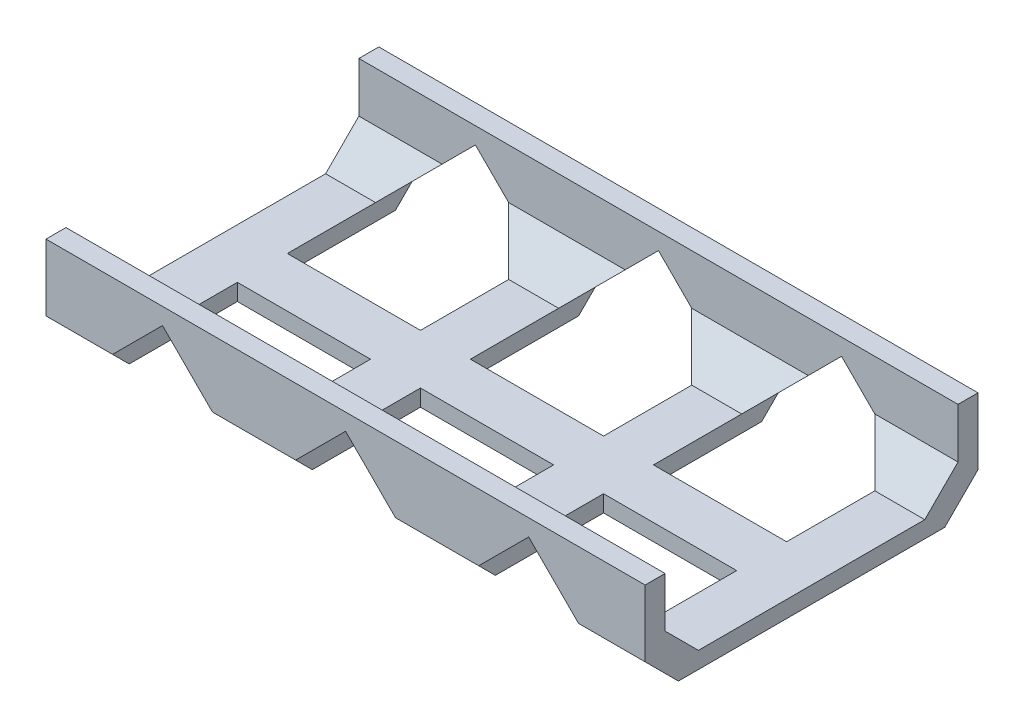
SolidWorks part; units mm, degrees
ref_plane "Front Plane" through (0, 0, 0) normal (0, 0, 1) x (1, 0, 0)
ref_plane "Top Plane" through (0, 0, 0) normal (0, 1, 0) x (1, 0, 0)
ref_plane "Right Plane" through (0, 0, 0) normal (1, 0, 0) x (0, 0, -1)
sketch "Sketch1" plane through (0, 0, 0) normal (0, 1, 0) x (1, 0, 0)
  line L1 (-57.15, -4.7625) -> (57.15, -4.7625)
  line L2 (-57.15, -4.7625) -> (-57.15, 4.7625)
  line L3 (-57.15, 4.7625) -> (57.15, 4.7625)
  line L4 (57.15, -4.7625) -> (57.15, 4.7625)
  line L5 (-57.15, -4.7625) -> (57.15, 4.7625) construction
  line L6 (-57.15, 4.7625) -> (57.15, -4.7625) construction
  point P0 (0, 0)
  dimension "D1" = 9.525
  dimension "D2" = 114.3
extrude "Boss-Extrude1" add sketch "Sketch1" along normal blind 3.175
sketch "Sketch2" plane through (0, 3.175, 0) normal (0, 1, 0) x (1, 0, 0)
  line L0 (0, 0) -> (50000, 0) construction
  line L1 (-57.15, 4.7625) -> (-57.15, -4.7625) construction
  line L2 (-47.625, -31.75) -> (-57.15, -31.75)
  line L3 (-47.625, -31.75) -> (-47.625, 31.75)
  line L4 (-47.625, 31.75) -> (-57.15, 31.75)
  line L5 (-57.15, -31.75) -> (-57.15, 31.75)
  line L6 (-47.625, -31.75) -> (-57.15, 31.75) construction
  line L7 (-47.625, 31.75) -> (-57.15, -31.75) construction
  line L14 (47.625, -31.75) -> (57.15, -31.75)
  line L15 (47.625, -31.75) -> (47.625, 31.75)
  line L16 (47.625, 31.75) -> (57.15, 31.75)
  line L17 (57.15, -31.75) -> (57.15, 31.75)
  line L18 (47.625, -31.75) -> (57.15, 31.75) construction
  line L19 (47.625, 31.75) -> (57.15, -31.75) construction
  line L20 (12.7, -31.75) -> (22.225, -31.75)
  line L21 (12.7, -31.75) -> (12.7, 31.75)
  line L22 (12.7, 31.75) -> (22.225, 31.75)
  line L23 (22.225, -31.75) -> (22.225, 31.75)
  line L24 (12.7, -31.75) -> (22.225, 31.75) construction
  line L25 (12.7, 31.75) -> (22.225, -31.75) construction
  line L26 (-22.225, -31.75) -> (-12.7, -31.75)
  line L27 (-22.225, -31.75) -> (-22.225, 31.75)
  line L28 (-22.225, 31.75) -> (-12.7, 31.75)
  line L29 (-12.7, -31.75) -> (-12.7, 31.75)
  line L30 (-22.225, -31.75) -> (-12.7, 31.75) construction
  line L31 (-22.225, 31.75) -> (-12.7, -31.75) construction
  line L32 (57.15, -4.7625) -> (57.15, 4.7625) construction
  line L33 (-47.625, -31.75) -> (-22.225, -31.75) construction
  line L34 (-12.7, -31.75) -> (12.7, -31.75) construction
  line L36 (22.225, -31.75) -> (47.625, -31.75) construction
  point P3 (-52.3875, 0)
  point P8 (0, 0)
  point P9 (2.3098, -33.3038)
  point P11 (1.6538, -31.75)
  point P12 (12.1782, -31.75)
  point P13 (52.3875, 0)
  point P18 (17.4625, 0)
  point P23 (-17.4625, 0)
  point P32 (-57.15, 32.2913)
  point P33 (-47.8757, -31.75)
  dimension "D1" = 63.5
  dimension "D2" = 9.525
extrude "Boss-Extrude2" add sketch "Sketch2" against normal blind 3.175
sketch "Sketch3" plane through (0, 3.175, 0) normal (0, 1, 0) x (1, 0, 0)
  line L0 (-57.15, 31.75) -> (-57.15, -31.75) construction
  line L1 (-47.625, -31.75) -> (-57.15, -31.75)
  line L2 (-47.625, -31.75) -> (-47.625, -27.94)
  line L3 (-47.625, -27.94) -> (-57.15, -27.94)
  line L4 (-57.15, -31.75) -> (-57.15, -27.94)
  line L5 (-22.225, -4.7625) -> (-22.225, -31.75) construction
  line L6 (-12.7, -31.75) -> (-22.225, -31.75)
  line L7 (-12.7, -31.75) -> (-12.7, -27.94)
  line L8 (-12.7, -27.94) -> (-22.225, -27.94)
  line L9 (-22.225, -31.75) -> (-22.225, -27.94)
  line L10 (12.7, -4.7625) -> (12.7, -31.75) construction
  line L11 (22.225, -31.75) -> (12.7, -31.75)
  line L12 (22.225, -31.75) -> (22.225, -27.94)
  line L13 (22.225, -27.94) -> (12.7, -27.94)
  line L14 (12.7, -31.75) -> (12.7, -27.94)
  line L15 (47.625, -4.7625) -> (47.625, -31.75) construction
  line L16 (57.15, -31.75) -> (47.625, -31.75)
  line L17 (57.15, -31.75) -> (57.15, -27.94)
  line L18 (57.15, -27.94) -> (47.625, -27.94)
  line L19 (47.625, -31.75) -> (47.625, -27.94)
  line L20 (47.625, 31.75) -> (47.625, 4.7625) construction
  line L21 (57.15, 31.75) -> (47.625, 31.75)
  line L22 (57.15, 31.75) -> (57.15, 27.94)
  line L23 (57.15, 27.94) -> (47.625, 27.94)
  line L24 (47.625, 31.75) -> (47.625, 27.94)
  line L25 (12.7, 31.75) -> (12.7, 4.7625) construction
  line L26 (22.225, 31.75) -> (12.7, 31.75)
  line L27 (22.225, 31.75) -> (22.225, 27.94)
  line L28 (22.225, 27.94) -> (12.7, 27.94)
  line L29 (12.7, 31.75) -> (12.7, 27.94)
  line L30 (-22.225, 31.75) -> (-22.225, 4.7625) construction
  line L31 (-12.7, 31.75) -> (-22.225, 31.75)
  line L32 (-12.7, 31.75) -> (-12.7, 27.94)
  line L33 (-12.7, 27.94) -> (-22.225, 27.94)
  line L34 (-22.225, 31.75) -> (-22.225, 27.94)
  line L36 (-47.625, 31.75) -> (-57.15, 31.75)
  line L37 (-47.625, 31.75) -> (-47.625, 27.94)
  line L38 (-47.625, 27.94) -> (-57.15, 27.94)
  line L39 (-57.15, 31.75) -> (-57.15, 27.94)
  dimension "D1" = 3.81
  dimension "D2" = 3.81
extrude "Boss-Extrude3" add sketch "Sketch3" along normal blind 12.7
sketch "Sketch4" plane through (0, 15.875, 0) normal (0, 1, 0) x (1, 0, 0)
  line L1 (-57.15, -31.75) -> (57.15, -31.75)
  line L2 (-57.15, -31.75) -> (-57.15, -27.94)
  line L3 (-57.15, -27.94) -> (57.15, -27.94)
  line L4 (57.15, -31.75) -> (57.15, -27.94)
  line L5 (57.15, 27.94) -> (-57.15, 27.94)
  line L6 (57.15, 27.94) -> (57.15, 31.75)
  line L7 (57.15, 31.75) -> (-57.15, 31.75)
  line L8 (-57.15, 27.94) -> (-57.15, 31.75)
extrude "Boss-Extrude4" add sketch "Sketch4" along normal blind 3.175
chamfer "Chamfer1" distance 12.7 angle 45 12 edges at (47.625, 15.875, -29.845) (22.225, 15.875, -29.845) (12.7, 15.875, -29.845) (-12.7, 15.875, -29.845) (-22.225, 15.875, -29.845) (-47.625, 15.875, -29.845) (47.625, 15.875, 29.845) (22.225, 15.875, 29.845) (12.7, 15.875, 29.845) (-12.7, 15.875, 29.845) (-22.225, 15.875, 29.845) (-47.625, 15.875, 29.845)
chamfer "Chamfer2" distance 6.35 angle 45 16 edges at (-52.3875, 3.175, -27.94) (-17.4625, 3.175, -27.94) (17.4625, 3.175, -27.94) (52.3875, 3.175, -27.94) (52.3875, 3.175, 27.94) (17.4625, 3.175, 27.94) (-17.4625, 3.175, 27.94) (-52.3875, 0, -31.75) (-17.4625, 0, -31.75) (17.4625, 0, -31.75) (52.3875, 0, -31.75) (52.3875, 0, 31.75) (17.4625, 0, 31.75) (-17.4625, 0, 31.75) (-52.3875, 0, 31.75) (-52.3875, 3.175, 27.94)
